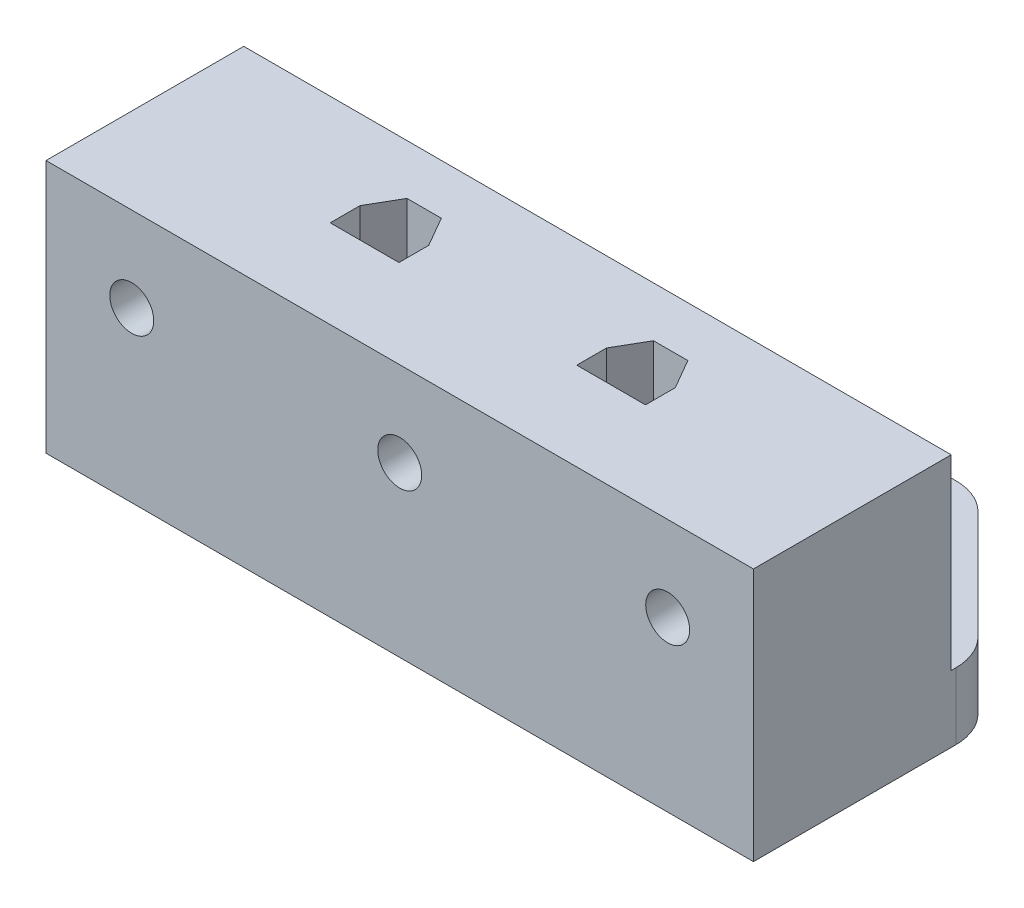
SolidWorks part; units mm, degrees
ref_plane "Front Plane" through (0, 0, 0) normal (0, 0, 1) x (1, 0, 0)
ref_plane "Top Plane" through (0, 0, 0) normal (0, 1, 0) x (1, 0, 0)
ref_plane "Right Plane" through (0, 0, 0) normal (1, 0, 0) x (0, 0, -1)
sketch "Sketch1" plane through (0, 0, 0) normal (0, 1, 0) x (1, 0, 0)
  line L0 (0, -31.1) -> (62, -31.1)
  line L1 (0, 0) -> (62, 0)
  line L2 (0, 0) -> (0, -68)
  line L3 (0, -68) -> (62, -68)
  line L4 (62, 0) -> (62, -68)
  line L5 (4.7928, -40.445) -> (11.2072, -40.445)
  line L6 (11.2072, -40.445) -> (14.4144, -46)
  line L7 (14.4144, -46) -> (11.2072, -51.555)
  line L8 (11.2072, -51.555) -> (4.7928, -51.555)
  line L9 (4.7928, -51.555) -> (1.5856, -46)
  line L10 (1.5856, -46) -> (4.7928, -40.445)
  line L11 (8, -40.445) -> (8, -51.555) construction
  line L12 (14.4144, -46) -> (1.5856, -46)
  line L13 (11.2072, -40.445) -> (8, -46)
  line L14 (8, -46) -> (11.2072, -51.555)
  line L15 (8, -46) -> (4.7928, -40.445)
  line L16 (8, -46) -> (4.7928, -51.555)
  line L17 (14.4144, -46) -> (14.4144, -51.555)
  line L18 (14.4144, -51.555) -> (1.5856, -51.555)
  line L19 (1.5856, -51.555) -> (1.5856, -46)
  line L20 (31, -68) -> (31, 0) construction
  line L21 (60.4144, -51.555) -> (60.4144, -46)
  line L22 (60.4144, -46) -> (57.2072, -40.445)
  line L23 (47.5856, -51.555) -> (60.4144, -51.555)
  line L24 (47.5856, -46) -> (47.5856, -51.555)
  line L25 (50.7928, -40.445) -> (47.5856, -46)
  line L26 (57.2072, -40.445) -> (50.7928, -40.445)
  line L27 (62, -31.1) -> (97, -31.1)
  line L28 (97, -31.1) -> (97, -68)
  line L29 (97, -68) -> (62, -68)
  line L30 (0, -31.1) -> (-35, -31.1)
  line L31 (-35, -31.1) -> (-35, -68)
  line L32 (-35, -68) -> (0, -68)
  circle A0 centre (8, -12) radius 3.3235
  circle A1 centre (54, -12) radius 3.3235
  circle A2 centre (8, -46) radius 3.3235
  circle A3 centre (54, -46) radius 3.3235
  point P24 (8, -46)
  point P25 (8, -46)
  dimension "D5" = 6.647
  dimension "D1" = 68
  dimension "D2" = 62
  dimension "D3" = 34
  dimension "D4" = 46
  dimension "D6" = 12
  dimension "D7" = 8
  dimension "D8" = 31.1
  dimension "D9" = 11.11
  dimension "D10" = 60
  dimension "D11" = 35
extrude "Boss-Extrude1" add sketch "Sketch1" along normal blind 12.446 contours L4 L1 L2 L0 A1 A0 region at (31, 0, 15.6825)
extrude "Boss-Extrude2" add sketch "Sketch1<3>" along normal blind 47.3 contours L31 L32 L2 L30 | L4 L0 L2 L3 L26 L22 L21 L23 L24 L25 L18 L19 L10 L5 L6 L17 L8 | L29 L28 L27 L4 region at (31, 0, 49.9197) region at (-17.5, 0, 49.55) region at (79.5, 0, 49.55)
sketch "Sketch1<3>" plane through (0, 0, 0) normal (0, 1, 0) x (1, 0, 0) same geometry as "Sketch1"
extrude "Boss-Extrude3" add sketch "Sketch1<4>" along normal blind 21 contours L19 L18 L9 | A2 L12 L9 L16 | A2 L16 L8 L14 | A2 L14 L7 L12 | L18 L17 L7 | A2 L12 L6 L13 | A2 L13 L5 L15 | A2 L15 L10 L12 | L22 L26 L25 L24 L23 L21 A3 region at (4.132, 0, 43.7668) region at (8, 0, 41.5336) region at (11.868, 0, 43.7668) region at (4.132, 0, 48.2332) region at (2.6547, 0, 49.7033) region at (13.3453, 0, 49.7033) region at (11.868, 0, 48.2332) region at (8, 0, 50.4664) region at (54, 0, 51.3853)
sketch "Sketch1<4>" plane through (0, 0, 0) normal (0, 1, 0) x (1, 0, 0) same geometry as "Sketch1"
ref_plane "Plane1" through (0, 0, 68) normal (0, 0, -1) x (-1, 0, 0)
sketch "Sketch2" plane through (0, 0, 68) normal (0, 0, -1) x (-1, 0, 0)
  line L0 (35, 0) -> (0, 0) construction
  line L2 (35, 47.3) -> (35, 0) construction
  circle A0 centre (19, 31.47) radius 4.1
  circle A1 centre (-31, 31.47) radius 4.1
  circle A2 centre (-81, 31.47) radius 4.1
  point P6 (0, 0)
  dimension "D2" = 8.2
  dimension "D1" = 31.47
  dimension "D4" = 50
  dimension "D5" = 50
  dimension "D3" = 66
extrude "Cut-Extrude1" cut sketch "Sketch2" along normal up to surface (36.9 mm away) up to face at (31, 14.9365, 31.1)
chamfer "Chamfer1" distance 40 angle 45 2 edges at (62, 6.223, 31.1) (0, 6.223, 31.1)
fillet "Fillet3" radius 10 4 edges at (-35, 6.223, 26.1) (97, 6.223, 26.1) (70.9, 6.223, 0) (-8.9, 6.223, 0)
equation "\"D4@Sketch2\"=\"D5@Sketch2\""
